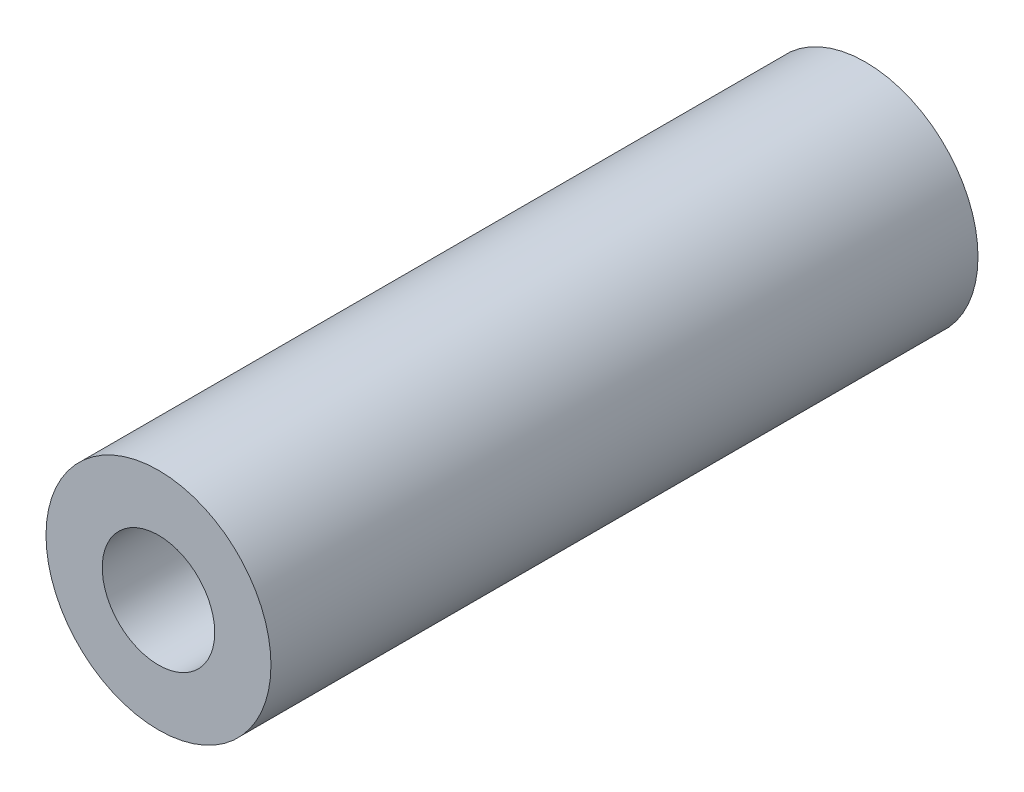
SolidWorks part; units mm, degrees
ref_plane "Front" through (0, 0, 0) normal (0, 0, 1) x (1, 0, 0)
ref_plane "Top" through (0, 0, 0) normal (0, 1, 0) x (1, 0, 0)
ref_plane "Right" through (0, 0, 0) normal (1, 0, 0) x (0, 0, -1)
sketch "Sketch1" plane through (0, 0, 0) normal (0, 0, 1) x (1, 0, 0)
  circle A0 centre (0, 0) radius 1.75
  circle A1 centre (0, 0) radius 3.5
extrude "Boss-Extrude1" add sketch "Sketch1" along normal blind 22
